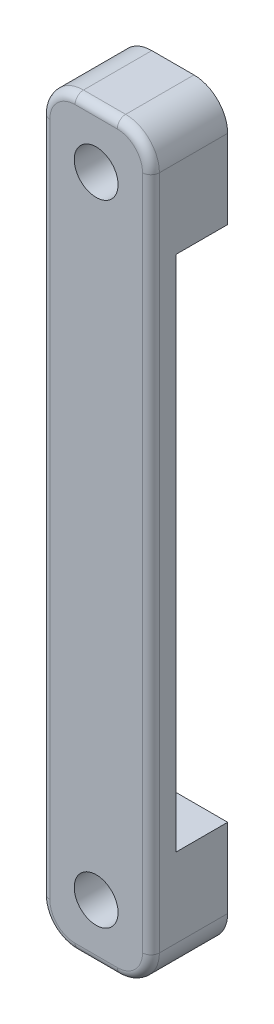
SolidWorks part; units mm, degrees
ref_plane "Front Plane" through (0, 0, 0) normal (0, 0, 1) x (1, 0, 0)
ref_plane "Top Plane" through (0, 0, 0) normal (0, 1, 0) x (1, 0, 0)
ref_plane "Right Plane" through (0, 0, 0) normal (1, 0, 0) x (0, 0, -1)
sketch "Sketch1" plane through (0, 0, 0) normal (0, 0, 1) x (1, 0, 0)
  line L0 (-64.1444, 69.4911) -> (92.8306, 69.4911) construction
  line L1 (7.3028, 69.4911) -> (-5.6972, 69.4911)
  line L2 (7.3028, 69.4911) -> (7.3028, -18.6589)
  line L3 (7.3028, -18.6589) -> (-5.6972, -18.6589)
  line L4 (-5.6972, 69.4911) -> (-5.6972, -18.6589)
  line L7 (92.8306, -18.6589) -> (-64.1444, -18.6589) construction
  circle A0 centre (0.8028, 32.3036) radius 2.5 construction
  point P0 (-3.6972, -49.1589)
  point P7 (5.3028, 38.9911)
  point P11 (5.3028, -47.1489)
  dimension "D1" = 4
  dimension "D2" = 4
extrude "Boss-Extrude1" add sketch "Sketch1" along normal blind 3
sketch "Sketch2" plane through (0, 0, 0) normal (0, 0, -1) x (-1, 0, 0)
  line L0 (-7.3028, -11.9714) -> (5.6972, -11.9714) construction
  line L5 (-7.3028, 62.8036) -> (5.6972, 62.8036) construction
  line L6 (-7.3028, -18.6589) -> (5.6972, -18.6589)
  line L7 (-7.3028, -18.6589) -> (-7.3028, -5.2839)
  line L9 (5.6972, -18.6589) -> (5.6972, -5.2839)
  line L10 (-7.3028, 25.4161) -> (5.6972, 25.4161)
  line L11 (-7.3028, 56.1161) -> (5.6972, 56.1161)
  line L12 (5.6972, 69.4911) -> (5.6972, 56.1161)
  line L13 (20.0444, -5.2839) -> (-60.3556, -5.2839) construction
  line L14 (-7.3028, -18.6589) -> (-7.3028, 69.4911) construction
  line L15 (-7.3028, -5.2839) -> (5.6972, -5.2839)
  line L16 (5.6972, 69.4911) -> (5.6972, -18.6589) construction
  line L17 (-7.3028, 69.4911) -> (-7.3028, 56.1161)
  line L18 (-7.3028, 69.4911) -> (5.6972, 69.4911)
  circle A1 centre (-0.8028, -11.9714) radius 2.6
  circle A4 centre (-0.8028, 62.8036) radius 2.6
  point P2 (-0.8028, 62.8036)
  dimension "D1" = 5.2
extrude "Boss-Extrude2" add sketch "Sketch2" along normal blind 6.1
extrude "Cut-Extrude1" cut sketch "Sketch2<3>" against normal through all contours A1 | A1 | A4 region at (0.8028, -11.9714, 0)
sketch "Sketch2<3>" plane through (0, 0, 0) normal (0, 0, -1) x (-1, 0, 0) same geometry as "Sketch2"
fillet "Fillet3" radius 4 4 edges at (7.3028, -18.6589, -1.55) (-5.6972, -18.6589, -1.55) (7.3028, 69.4911, -1.55) (-5.6972, 69.4911, -1.55)
fillet "Fillet2" radius 1 8 edges at (0.8028, -18.6589, 3) (0.8028, 69.4911, 3) (7.3028, 25.4161, 3) (-5.6972, 25.4161, 3) (-4.5256, 68.3195, 3) (6.1312, 68.3195, 3) (6.1312, -17.4874, 3) (-4.5256, -17.4874, 3)
equation "\"D2@Sketch1\"=\"D1@Sketch1\""
